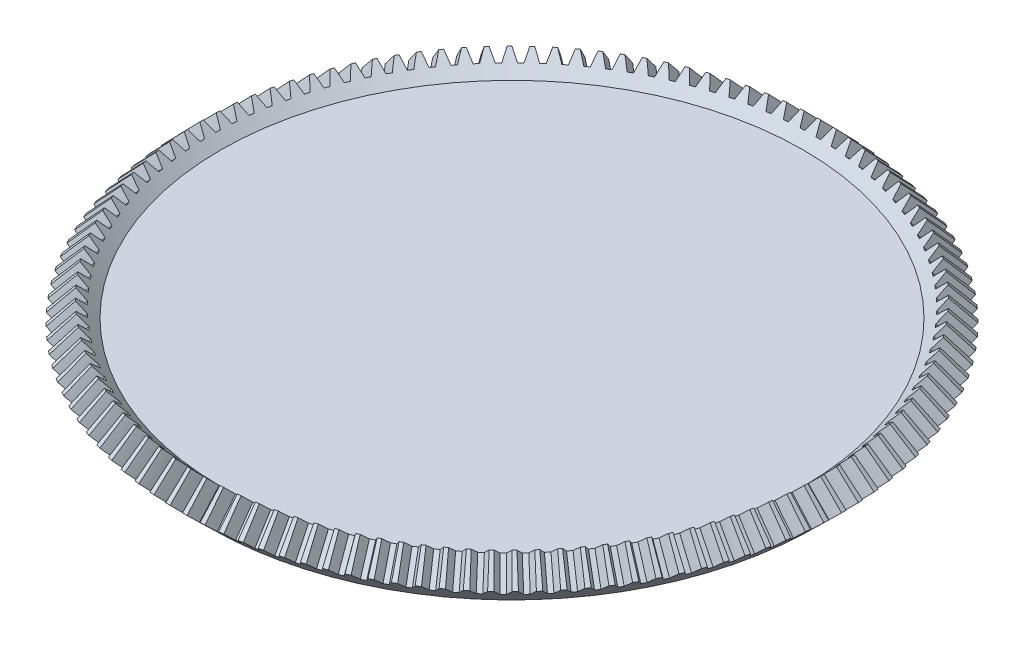
SolidWorks part; units mm, degrees
ref_plane "Front Plane" through (0, 0, 0) normal (0, 0, 1) x (1, 0, 0)
ref_plane "Top Plane" through (0, 0, 0) normal (0, 1, 0) x (1, 0, 0)
ref_plane "Right Plane" through (0, 0, 0) normal (1, 0, 0) x (0, 0, -1)
sketch "Sketch11" plane through (0, 0, 0) normal (0, 0, 1) x (1, 0, 0)
  line L0 (0, 0) -> (0, 120) construction
  line L1 (0, 0) -> (-90, 0) construction
  line L2 (0, 0) -> (0, -49.4819) construction
  line L3 (0, -49.4819) -> (-91.0605, -49.4819) construction
  line L4 (0, -79.9822) -> (-88.82, -79.9822) construction
  line L5 (-90, 120) -> (0.0147, 210.0147) construction
  line L6 (-90, 120) -> (-61.5021, 120) construction
  line L7 (0.0147, 210.0147) -> (-96.0377, 116.1829) construction
  line L8 (0.0147, 210.0147) -> (-92.7643, 115.0069) construction
  line L9 (0.0147, 210.0147) -> (0.0147, 146.7224) construction
  line L10 (-90, 120) -> (-88.9191, 118.9445)
  line L11 (-90, 120) -> (-91.0402, 121.0648)
  line L12 (-91.0402, 121.0648) -> (-85.3176, 126.6551)
  line L13 (-85.3176, 126.6551) -> (-83.3068, 124.6916)
  line L14 (-83.3068, 124.6916) -> (-88.9191, 118.9445)
  line L15 (-88.9191, 118.9445) -> (-81.7646, 111.9578)
  line L16 (-81.7646, 111.9578) -> (0, 111.9578)
  line L17 (-83.3068, 124.6916) -> (-78.6153, 120)
  line L18 (-78.6153, 120) -> (0, 120)
  line L19 (0, 120) -> (0, 111.9578)
  dimension "D1" = 90
  dimension "D2" = 91.0605
  dimension "D3" = 88.82
  dimension "D4" = 45
  dimension "D5" = 127.3
  dimension "D6" = 45.67
  dimension "D7" = 44.32
revolve "Revolve1" add sketch "Sketch11" angle 360 about L0 region at (-44.1343, 116.2063, 0)
sketch "Sketch12" plane through (0, 0, 0) normal (1, 0, 0) x (0, 0, -1)
  line L0 (-88.9191, 118.9445) -> (0, 207.8636) construction
  line L1 (0, 111.9578) -> (0, 207.8636) construction
  line L2 (-81.7646, 111.9578) -> (81.7646, 111.9578) construction
  line L3 (-88.9191, 118.9445) -> (22.2775, 118.9445) construction
  line L4 (88.9191, 118.9445) -> (-88.9191, 118.9445) construction
  dimension "D1" = 45
sketch "Sketch13" plane through (0, 111.9578, 0) normal (0, -1, 0) x (1, 0, 0)
  line L0 (0, 81.7646) -> (-67.0377, 81.7646) construction
  circle A0 centre (0, 0) radius 81.7646 construction
ref_plane "Plane2" through (0, 16.4367, -16.0511) normal (0, 0.7154, -0.6987) x (1, 0, 0)
sketch "Sketch14" plane through (0, 16.4367, -16.0511) normal (0, 0.7154, -0.6987) x (1, 0, 0)
  arc A1 (-1.0406, -143.4694) -> (0, -146.7194) centre (40.9134, -131.8281) ccw
  arc A2 (-2.2935, -143.4526) -> (-3.4211, -146.6734) centre (-43.9195, -130.688) cw
  arc A3 (-3.4211, -146.6734) -> (0, -146.7194) centre (0, -19.4194) ccw
  arc A4 (-2.2935, -143.4526) -> (-1.0406, -143.4694) centre (0, -19.4194) ccw
  point P1 (0, 0)
ref_plane "Plane3" through (0, 107.5134, -104.9912) normal (0, 0.7154, -0.6987) x (1, 0, 0)
sketch "Sketch15" plane through (0, 107.5134, -104.9912) normal (0, 0.7154, -0.6987) x (1, 0, 0)
  circle A0 centre (0, -145.2557) radius 0.05
extrude "Cut-Extrude1" cut sketch "Sketch14" along normal blind 12
pattern_circular "CirPattern1" count 120 over 360 about axis through (0, 118.9445, 0) along (0, -1, 0) of "Cut-Extrude1"
